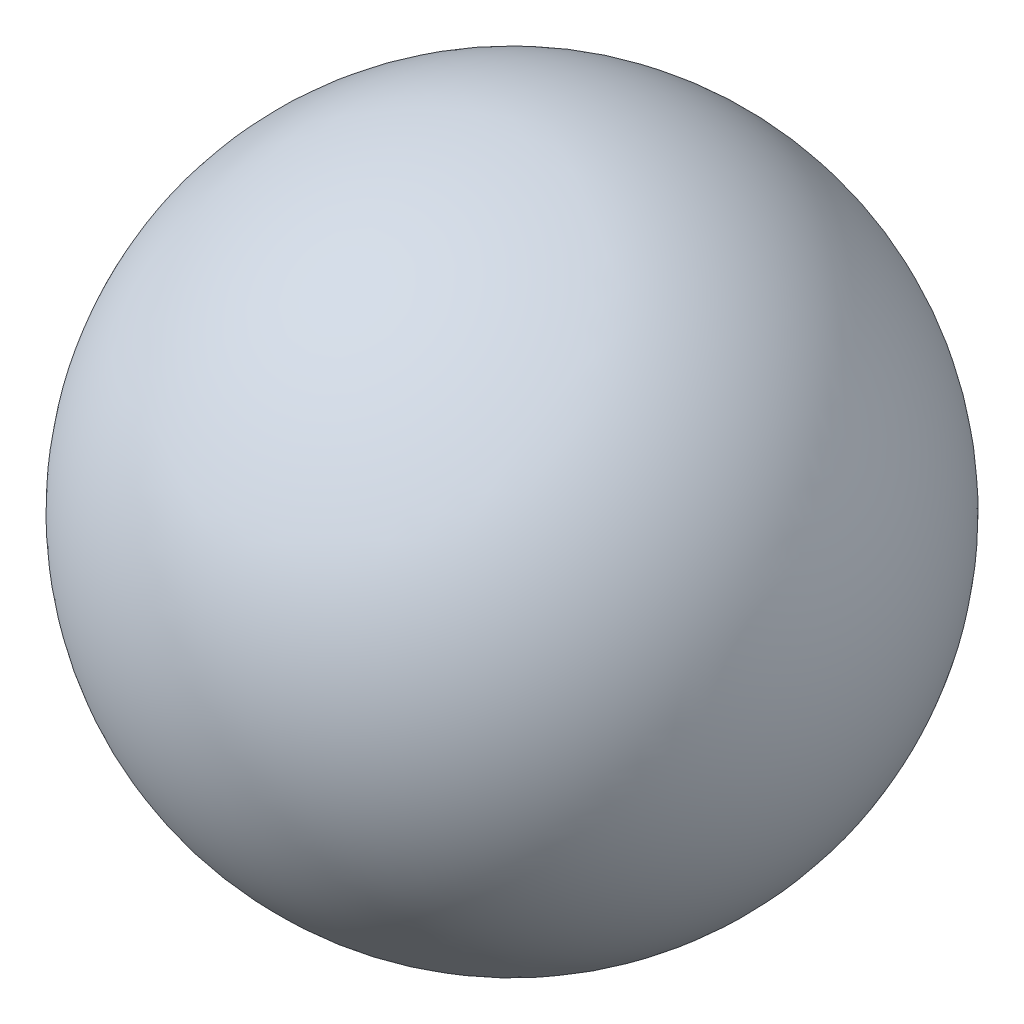
SolidWorks part; units mm, degrees
ref_plane "前视基准面" through (0, 0, 0) normal (0, 0, 1) x (1, 0, 0)
ref_plane "上视基准面" through (0, 0, 0) normal (0, 1, 0) x (1, 0, 0)
ref_plane "右视基准面" through (0, 0, 0) normal (1, 0, 0) x (0, 0, -1)
other "Configuration Table"
sketch "草图1" plane through (0, 0, 0) normal (0, 1, 0) x (1, 0, 0)
  line L0 (-2.5, 0) -> (2.5, 0) construction
  circle A8 centre (0, 0) radius 2.5
  dimension "D1" = 5
revolve "旋转3" add sketch "草图1" angle 360 about L0 region at (0, 0, 1.061)
sketch "草图2" plane through (0, 0, 0) normal (0, 1, 0) x (1, 0, 0)
  circle A0 centre (-32.9, 0) radius 32.9
  point P2 (0, 0)
  dimension "D1" = 65.8
